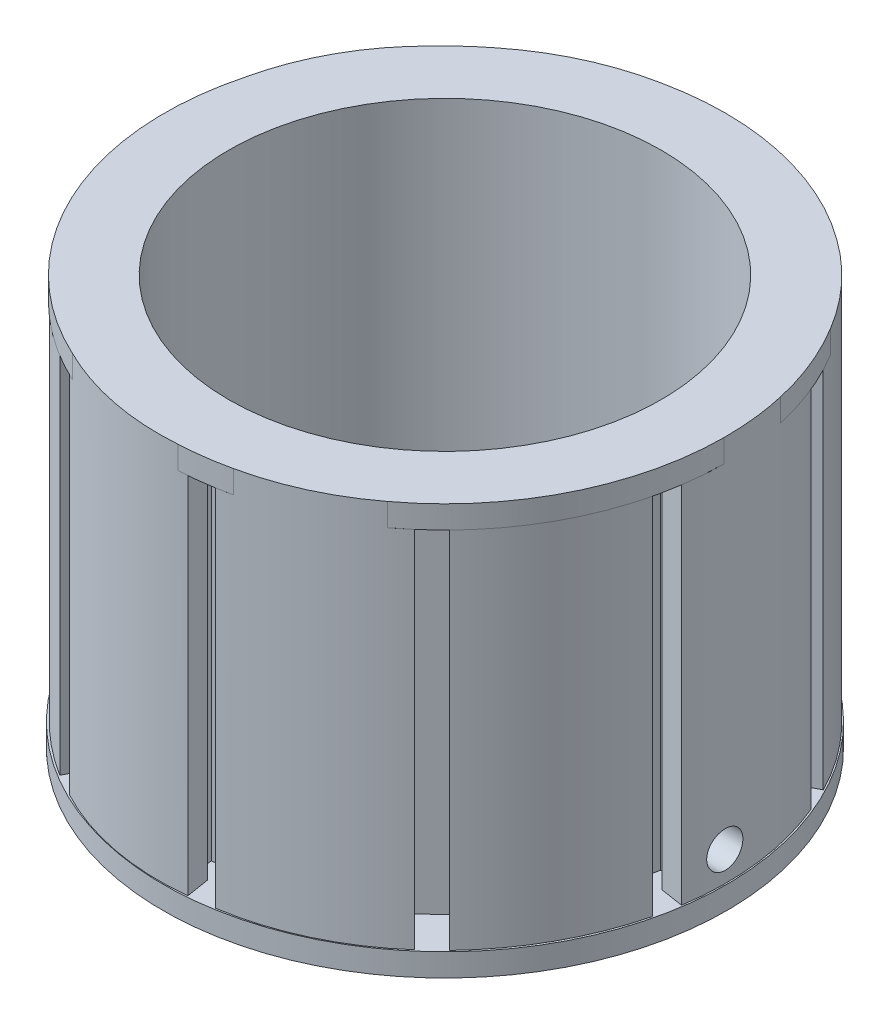
SolidWorks part; units mm, degrees
ref_plane "Alzado" through (0, 0, 0) normal (0, 0, 1) x (1, 0, 0)
ref_plane "Planta" through (0, 0, 0) normal (0, 1, 0) x (1, 0, 0)
ref_plane "Vista lateral" through (0, 0, 0) normal (1, 0, 0) x (0, 0, -1)
sketch "Sketch3" plane through (0, 0, 0) normal (1, 0, 0) x (0, 0, -1)
  line L0 (0, 0) -> (0, 36)
  dimension "D1" = 36
sketch "Sketch2" plane through (0, 0, 0) normal (0, 1, 0) x (1, 0, 0)
  circle A0 centre (0, 0) radius 24.5
sketch "Sketch1" plane through (0, 0, 0) normal (0, 1, 0) x (1, 0, 0)
  line L0 (0, 0) -> (-24.5, 0) construction
  line L1 (0, 0) -> (0, 24.5) construction
  line L2 (0, 0) -> (0, -24.5) construction
  line L3 (0, 0) -> (24.5, 0) construction
  line L4 (0, 0) -> (-24.179, 4.7253) construction
  line L5 (-17.5664, 3.433) -> (-17.9871, 1.2802) construction
  line L6 (-17.9871, 1.2802) -> (-20.8948, 1.8485) construction
  line L7 (-20.8948, 1.8485) -> (-20.6845, 2.9249) construction
  line L8 (-20.6845, 2.9249) -> (-24.2404, 3.557) construction
  line L9 (-17.9871, 1.2802) -> (-17.1533, 5.5802) construction
  line L10 (-20.0277, 6.1489) -> (-20.2564, 5.0738) construction
  line L11 (-20.0277, 6.1489) -> (-17.1459, 5.586) construction
  line L12 (-20.2564, 5.0738) -> (-23.8257, 5.7083) construction
  line L13 (-24.2404, 3.557) -> (-20.6845, 2.9249)
  line L14 (-20.6845, 2.9249) -> (-20.8948, 1.8485)
  line L15 (-20.8948, 1.8485) -> (-17.9871, 1.2802)
  line L16 (-17.9871, 1.2802) -> (-17.1533, 5.5802)
  line L17 (-17.1533, 5.5802) -> (-20.0277, 6.1489)
  line L18 (-20.0277, 6.1489) -> (-20.2564, 5.0738)
  line L19 (-20.2564, 5.0738) -> (-23.8257, 5.7083)
  line L20 (-20.2564, 5.0738) -> (-20.6845, 2.9249) construction
  circle A1 centre (0, 0) radius 24.5 construction
  arc A3 (-23.8257, 5.7083) -> (-24.2404, 3.557) centre (0, 0) cw
  dimension "D1" = 24.5
  dimension "D2" = 24.5
  dimension "D3" = 24.5
  dimension "D4" = 24.5
ref_plane "Plane4" through (0, 0, 0) normal (1, 0, 0) x (0, 0, -1)
sketch "Sketch5" plane through (0, 0, 0) normal (0, 1, 0) x (1, 0, 0)
  line L0 (0.0754, 0) -> (-24.4246, 0) construction
  line L1 (0.0754, 0) -> (0.0754, 24.5) construction
  line L2 (0.0754, 0) -> (0.0754, -24.5) construction
  line L3 (0.0754, 0) -> (24.5754, 0) construction
  line L4 (0.0754, 0) -> (-24.1036, 4.7253) construction
  line L5 (-17.5664, 3.433) -> (-20.7765, 1.8254) construction
  line L6 (-20.7765, 1.8254) -> (-22.5261, 2.1673) construction
  line L7 (-22.5261, 2.1673) -> (-22.3133, 3.2565) construction
  line L8 (-22.3133, 3.2565) -> (-24.363, 3.5724) construction
  line L9 (-20.7765, 1.8254) -> (-19.9414, 6.1319) construction
  line L10 (-21.677, 6.4753) -> (-21.8849, 5.4053) construction
  line L11 (-21.677, 6.4753) -> (-17.1459, 5.586) construction
  line L12 (-21.8849, 5.4053) -> (-23.9442, 5.7227) construction
  line L13 (-24.363, 3.5724) -> (-22.3133, 3.2565)
  line L14 (-22.3133, 3.2565) -> (-22.5261, 2.1673)
  line L15 (-22.5261, 2.1673) -> (-20.7765, 1.8254)
  line L16 (-20.7765, 1.8254) -> (-19.9414, 6.1319)
  line L17 (-19.9414, 6.1319) -> (-21.677, 6.4753)
  line L18 (-21.677, 6.4753) -> (-21.8849, 5.4053)
  line L19 (-21.8849, 5.4053) -> (-23.9442, 5.7227)
  line L20 (-21.8849, 5.4053) -> (-22.3133, 3.2565) construction
  line L21 (0, 0) -> (-24.5, 0) construction
  line L22 (-17.6103, 17.2103) -> (-16.1377, 15.7499)
  line L23 (-16.1377, 15.7499) -> (-16.9501, 14.9939)
  line L24 (-16.9501, 14.9939) -> (-15.7356, 13.6889)
  line L25 (-15.7356, 13.6889) -> (-12.5287, 16.6821)
  line L26 (-12.5287, 16.6821) -> (-13.731, 17.98)
  line L27 (-13.731, 17.98) -> (-14.5281, 17.2367)
  line L28 (-14.5281, 17.2367) -> (-16.0075, 18.7038)
  line L29 (-4.1311, 24.2745) -> (-3.7981, 22.2275)
  line L30 (-3.7981, 22.2275) -> (-4.8997, 22.0934)
  line L31 (-4.8997, 22.0934) -> (-4.6843, 20.3237)
  line L32 (-4.6843, 20.3237) -> (-0.3305, 20.8603)
  line L33 (-0.3305, 20.8603) -> (-0.5402, 22.6171)
  line L34 (-0.5402, 22.6171) -> (-1.622, 22.4842)
  line L35 (-1.622, 22.4842) -> (-1.9565, 24.5407)
  line L36 (10.9261, 22.0667) -> (9.9923, 20.2149)
  line L37 (9.9923, 20.2149) -> (9.0222, 20.7539)
  line L38 (9.0222, 20.7539) -> (8.1563, 19.1955)
  line L39 (8.1563, 19.1955) -> (11.994, 17.0706)
  line L40 (11.994, 17.0706) -> (12.8569, 18.6151)
  line L41 (12.8569, 18.6151) -> (11.9036, 19.1435)
  line L42 (11.9036, 19.1435) -> (12.8418, 21.0039)
  line L43 (21.8098, 11.4301) -> (19.9659, 10.4809)
  line L44 (19.9659, 10.4809) -> (19.4979, 11.4872)
  line L45 (19.4979, 11.4872) -> (17.8814, 10.7354)
  line L46 (17.8814, 10.7354) -> (19.7372, 6.7605)
  line L47 (19.7372, 6.7605) -> (21.3432, 7.5028)
  line L48 (21.3432, 7.5028) -> (20.8825, 8.4906)
  line L49 (20.8825, 8.4906) -> (22.735, 9.4443)
  line L50 (24.363, -3.5724) -> (22.3133, -3.2565)
  line L51 (22.3133, -3.2565) -> (22.5261, -2.1673)
  line L52 (22.5261, -2.1673) -> (20.7765, -1.8254)
  line L53 (20.7765, -1.8254) -> (19.9414, -6.1319)
  line L54 (19.9414, -6.1319) -> (21.677, -6.4753)
  line L55 (21.677, -6.4753) -> (21.8849, -5.4053)
  line L56 (21.8849, -5.4053) -> (23.9442, -5.7227)
  line L57 (17.6103, -17.2103) -> (16.1377, -15.7499)
  line L58 (16.1377, -15.7499) -> (16.9501, -14.9939)
  line L59 (16.9501, -14.9939) -> (15.7356, -13.6889)
  line L60 (15.7356, -13.6889) -> (12.5287, -16.6821)
  line L61 (12.5287, -16.6821) -> (13.731, -17.98)
  line L62 (13.731, -17.98) -> (14.5281, -17.2367)
  line L63 (14.5281, -17.2367) -> (16.0075, -18.7038)
  line L64 (4.1311, -24.2745) -> (3.7981, -22.2275)
  line L65 (3.7981, -22.2275) -> (4.8997, -22.0934)
  line L66 (4.8997, -22.0934) -> (4.6843, -20.3237)
  line L67 (4.6843, -20.3237) -> (0.3305, -20.8603)
  line L68 (0.3305, -20.8603) -> (0.5402, -22.6171)
  line L69 (0.5402, -22.6171) -> (1.622, -22.4842)
  line L70 (1.622, -22.4842) -> (1.9565, -24.5407)
  line L71 (-10.9261, -22.0667) -> (-9.9923, -20.2149)
  line L72 (-9.9923, -20.2149) -> (-9.0222, -20.7539)
  line L73 (-9.0222, -20.7539) -> (-8.1563, -19.1955)
  line L74 (-8.1563, -19.1955) -> (-11.994, -17.0706)
  line L75 (-11.994, -17.0706) -> (-12.8569, -18.6151)
  line L76 (-12.8569, -18.6151) -> (-11.9036, -19.1435)
  line L77 (-11.9036, -19.1435) -> (-12.8418, -21.0039)
  line L78 (-21.8098, -11.4301) -> (-19.9659, -10.4809)
  line L79 (-19.9659, -10.4809) -> (-19.4979, -11.4872)
  line L80 (-19.4979, -11.4872) -> (-17.8814, -10.7354)
  line L81 (-17.8814, -10.7354) -> (-19.7372, -6.7605)
  line L82 (-19.7372, -6.7605) -> (-21.3432, -7.5028)
  line L83 (-21.3432, -7.5028) -> (-20.8825, -8.4906)
  line L84 (-20.8825, -8.4906) -> (-22.735, -9.4443)
  arc A12 (-24.363, 3.5724) -> (-22.735, -9.4443) centre (-0.5159, -0.0552) ccw
  arc A13 (-21.8098, -11.4301) -> (-12.8418, -21.0039) centre (0.6864, 0.6556) ccw
  arc A14 (-10.9261, -22.0667) -> (1.9565, -24.5407) centre (-0.4657, -2.3758) ccw
  arc A15 (4.1311, -24.2745) -> (16.0075, -18.7038) centre (0.5253, -1.1418) ccw
  arc A19 (12.8418, 21.0039) -> (21.8098, 11.4301) centre (0.8003, 0.737) cw
  arc A20 (22.735, 9.4443) -> (24.363, -3.5724) centre (0.6279, 0.0692) cw
  arc A23 (17.6103, -17.2103) -> (23.9442, -5.7227) centre (-0.9852, 0.5326) ccw
  arc A24 (-1.9565, 24.5407) -> (10.9261, 22.0667) centre (-0.0263, -0.1859) cw
  arc A25 (-23.9442, 5.7227) -> (-17.6103, 17.2103) centre (-3.0155, 1.6732) cw
  arc A26 (-16.0075, 18.7038) -> (-4.1311, 24.2745) centre (-0.6941, 1.5015) cw
  point P96 (0, 0)
  dimension "D1" = 10
extrude "Boss-Extrude1" add sketch "Sketch5" along normal blind 36
sketch "Sketch6" plane through (0, 36, 0) normal (0, 1, 0) x (1, 0, 0)
  circle A1 centre (0, 0) radius 4
  dimension "D1" = 8
extrude "Cut-Extrude1" cut sketch "Sketch6" against normal through all
sketch "Sketch7" plane through (0, 36, 0) normal (0, 1, 0) x (1, 0, 0)
  circle A1 centre (0, 0) radius 19
  dimension "D1" = 38
extrude "Cut-Extrude2" cut sketch "Sketch7" against normal blind 28
sketch "Sketch8" plane through (0, 36, 0) normal (0, 1, 0) x (1, 0, 0)
  circle A0 centre (0, 0) radius 24.6403
  circle A1 centre (0, 0) radius 19
  dimension "D1" = 38
extrude "Boss-Extrude2" add sketch "Sketch8" against normal blind 2
sketch "Sketch9" plane through (0, 0, 0) normal (0, -1, 0) x (1, 0, 0)
  circle A0 centre (0, 0) radius 24.7655
  circle A1 centre (0, 0) radius 19
  dimension "D1" = 38
extrude "Boss-Extrude3" add sketch "Sketch9" against normal blind 2
ref_plane "Plane6" through (100, 0, 0) normal (1, 0, 0) x (0, 0, -1)
sketch "Sketch12" plane through (100, 0, 0) normal (1, 0, 0) x (0, 0, -1)
  line L0 (-24.7655, 0) -> (24.7655, 0) construction
  circle A0 centre (0, 4.5985) radius 1.585
  point P4 (-0.6193, 4.5985)
  point P5 (0, 4.5985)
  dimension "D1" = 3.17
  dimension "D2" = 4.5985
extrude "Cut-Extrude4" cut sketch "Sketch12" against normal through all and the other way through all
ref_plane "Plane9" through (0, 0, 0) normal (0, 0, 1) x (1, 0, 0)
ref_plane "Plane10" through (0, 0, 0) normal (1, 0, 0) x (0, 0, -1)
ref_plane "Plane11" through (0, 0, 0) normal (0.7071, 0, -0.7071) x (-0.7071, 0, -0.7071)
sketch "Sketch16" plane through (0, 0, 0) normal (0.7071, 0, -0.7071) x (-0.7071, 0, -0.7071)
  line L0 (-24.7655, 0) -> (24.7655, 0) construction
  circle A0 centre (0.6135, 4.5985) radius 1.585
  point P4 (-3.6439, 4.5985)
  point P5 (0, 4.5985)
  point P6 (-0.7924, 4.5985)
  point P7 (0.6135, 4.5985)
  dimension "D1" = 3.17
  dimension "D2" = 4.5985
